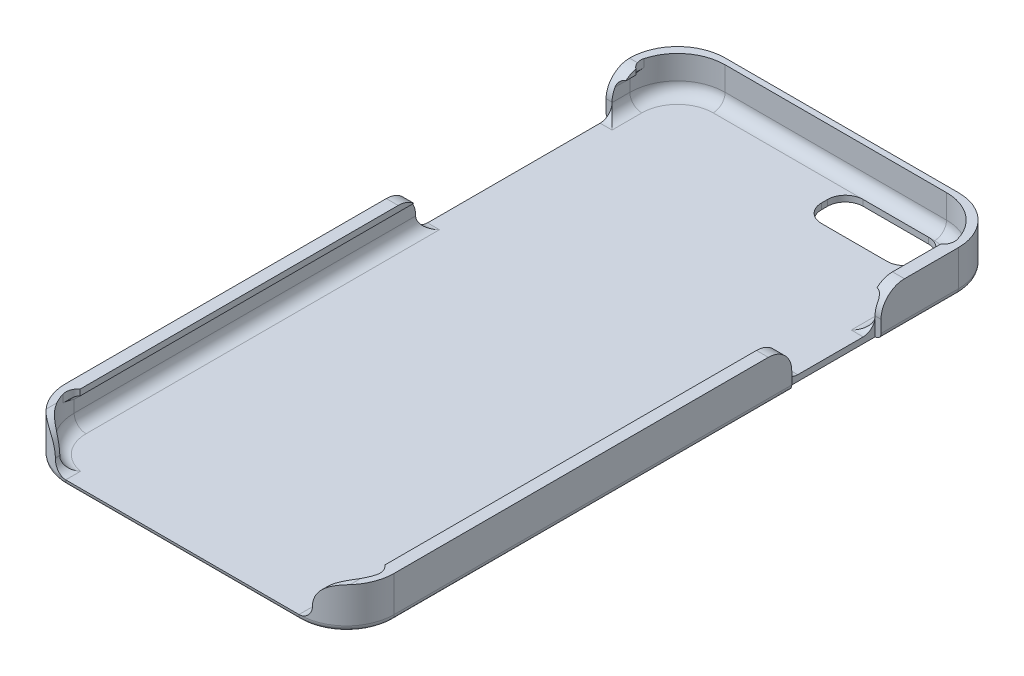
SolidWorks part; units mm, degrees
ref_plane "Front Plane" through (0, 0, 0) normal (0, 0, 1) x (1, 0, 0)
ref_plane "Top Plane" through (0, 0, 0) normal (0, 1, 0) x (1, 0, 0)
ref_plane "Right Plane" through (0, 0, 0) normal (1, 0, 0) x (0, 0, -1)
sketch "Sketch1" plane through (0, 0, 0) normal (0, 1, 0) x (1, 0, 0)
  line L1 (-35.052, 70.358) -> (35.052, 70.358)
  line L2 (-35.052, 70.358) -> (-35.052, -70.358)
  line L3 (-35.052, -70.358) -> (35.052, -70.358)
  line L4 (35.052, 70.358) -> (35.052, -70.358)
  line L5 (-35.052, 70.358) -> (35.052, -70.358) construction
  line L6 (-35.052, -70.358) -> (35.052, 70.358) construction
  point P0 (0, 0)
  dimension "D1" = 70.104
  dimension "D2" = 140.716
extrude "Boss-Extrude1" add sketch "Sketch1" along normal blind 1.27
sketch "Sketch2" plane through (0, 1.27, 0) normal (0, 1, 0) x (1, 0, 0)
  line L0 (-35.052, -70.358) -> (0, -70.358)
  line L1 (-35.052, -70.358) -> (35.052, -70.358) construction
  line L2 (-35.052, 70.358) -> (-35.052, -70.358)
  line L3 (-35.052, 70.358) -> (35.052, 70.358)
  line L4 (-33.782, 69.088) -> (-33.782, -69.088)
  line L5 (0, -70.358) -> (35.052, -70.358)
  line L6 (-33.782, -69.088) -> (33.782, -69.088)
  line L7 (35.052, 70.358) -> (35.052, -70.358)
  line L9 (33.782, 69.088) -> (33.782, -69.088)
  line L12 (-33.782, 69.088) -> (33.782, 69.088)
  dimension "D1" = 1.27
  dimension "D2" = 1.27
  dimension "D3" = 1.27
  dimension "D5" = 1.27
extrude "Boss-Extrude2" add sketch "Sketch2" along normal blind 7.62
sketch "Sketch3" plane through (-35.052, 0, 0) normal (-1, 0, 0) x (0, 0, 1)
  line L0 (-70.358, 8.89) -> (70.358, 8.89) construction
  line L1 (-55.118, 8.89) -> (-13.208, 8.89)
  line L2 (-55.118, 8.89) -> (-55.118, 1.27)
  line L3 (-55.118, 1.27) -> (-13.208, 1.27)
  line L4 (-13.208, 8.89) -> (-13.208, 1.27)
  line L5 (-70.358, 8.89) -> (-70.358, 0) construction
  line L6 (-70.358, 0) -> (70.358, 0) construction
  dimension "D1" = 15.24
  dimension "D2" = 57.15
  dimension "D3" = 1.27
extrude "Cut-Extrude1" cut sketch "Sketch3" against normal blind 1.27
sketch "Sketch5" plane through (35.052, 0, 0) normal (1, 0, 0) x (0, 0, -1)
  line L0 (-70.358, 8.89) -> (70.358, 8.89) construction
  line L1 (24.638, 8.89) -> (43.688, 8.89)
  line L2 (24.638, 8.89) -> (24.638, 1.27)
  line L3 (24.638, 1.27) -> (43.688, 1.27)
  line L4 (43.688, 8.89) -> (43.688, 1.27)
  line L5 (70.358, 8.89) -> (70.358, 0) construction
  line L6 (-70.358, 0) -> (70.358, 0) construction
  dimension "D1" = 26.67
  dimension "D2" = 45.72
  dimension "D3" = 1.27
extrude "Cut-Extrude2" cut sketch "Sketch5" against normal blind 1.27
sketch "Sketch6" plane through (0, 0, 70.358) normal (0, 0, 1) x (1, 0, 0)
  line L1 (-35.052, 8.89) -> (35.052, 8.89) construction
  line L2 (-27.432, 8.89) -> (27.432, 8.89)
  line L3 (-27.432, 8.89) -> (-27.432, 1.27)
  line L4 (-27.432, 1.27) -> (27.432, 1.27)
  line L8 (27.432, 8.89) -> (27.432, 1.27)
  line L9 (-35.052, 8.89) -> (-35.052, 0) construction
  line L10 (35.052, 8.89) -> (35.052, 0) construction
  line L11 (-35.052, 0) -> (35.052, 0) construction
  dimension "D1" = 7.62
  dimension "D2" = 7.62
  dimension "D3" = 1.27
extrude "Cut-Extrude3" cut sketch "Sketch6" against normal blind 1.27
sketch "Sketch7" plane through (0, 0, 0) normal (0, -1, 0) x (1, 0, 0)
  line L0 (35.052, 70.358) -> (35.052, -70.358) construction
  line L1 (26.162, -57.658) -> (4.572, -57.658)
  line L2 (26.162, -57.658) -> (26.162, -66.548)
  line L3 (26.162, -66.548) -> (4.572, -66.548)
  line L4 (4.572, -57.658) -> (4.572, -66.548)
  line L5 (35.052, -70.358) -> (-35.052, -70.358) construction
  dimension "D1" = 8.89
  dimension "D2" = 30.48
  dimension "D3" = 3.81
  dimension "D4" = 12.7
extrude "Cut-Extrude4" cut sketch "Sketch7" against normal blind 1.27
fillet "Fillet1" radius 10.16 4 edges at (33.782, 5.08, -69.088) (-33.782, 5.08, -69.088) (-33.782, 5.08, 69.088) (33.782, 5.08, 69.088)
fillet "Fillet2" radius 10.16 4 edges at (-35.052, 4.445, -70.358) (35.052, 4.445, -70.358) (35.052, 4.445, 70.358) (-35.052, 4.445, 70.358)
sketch "Sketch8" plane through (-33.782, 0, 0) normal (1, 0, 0) x (0, 0, -1)
  line L0 (58.928, 1.27) -> (58.928, 8.89) construction
  line L1 (55.118, 8.89) -> (58.928, 8.89)
  line L2 (55.118, 8.89) -> (55.118, 7.62)
  line L3 (55.118, 7.62) -> (58.928, 7.62)
  line L4 (58.928, 8.89) -> (58.928, 7.62)
  dimension "D1" = 1.27
extrude "Boss-Extrude3" add sketch "Sketch8" along normal blind 1.27
sketch "Sketch13" plane through (0, 0, -69.088) normal (0, 0, 1) x (1, 0, 0)
  line L0 (23.622, 1.27) -> (23.622, 8.89) construction
  line L1 (-23.622, 8.89) -> (23.622, 8.89)
  line L2 (-23.622, 8.89) -> (-23.622, 7.62)
  line L3 (-23.622, 7.62) -> (23.622, 7.62)
  line L4 (23.622, 8.89) -> (23.622, 7.62)
  dimension "D1" = 1.27
extrude "Boss-Extrude6" [suppressed] add sketch "Sketch13" along normal blind 1.27
sketch "Sketch14" plane through (33.782, 0, 0) normal (-1, 0, 0) x (0, 0, 1)
  line L0 (-43.688, 1.27) -> (-43.688, 8.89) construction
  line L1 (-58.928, 8.89) -> (-43.688, 8.89)
  line L2 (-58.928, 8.89) -> (-58.928, 7.62)
  line L3 (-58.928, 7.62) -> (-43.688, 7.62)
  line L4 (-43.688, 8.89) -> (-43.688, 7.62)
  dimension "D1" = 1.27
extrude "Boss-Extrude7" add sketch "Sketch14" along normal blind 1.27
sketch "Sketch19" plane through (33.782, 0, 0) normal (-1, 0, 0) x (0, 0, 1)
  line L1 (59.6694, 1.27) -> (59.6694, 8.89) construction
  line L2 (-24.638, 8.89) -> (59.6694, 8.89)
  line L3 (-24.638, 8.89) -> (-24.638, 7.62)
  line L4 (-24.638, 7.62) -> (59.6694, 7.62)
  line L5 (59.6694, 8.89) -> (59.6694, 7.62)
  dimension "D1" = 1.27
extrude "Boss-Extrude8" add sketch "Sketch19" along normal blind 1.27
sketch "Sketch20" plane through (-33.782, 0, 0) normal (1, 0, 0) x (0, 0, -1)
  line L1 (-59.6694, 8.89) -> (-59.6694, 1.27) construction
  line L2 (13.208, 8.89) -> (-59.6694, 8.89)
  line L3 (13.208, 8.89) -> (13.208, 7.62)
  line L4 (13.208, 7.62) -> (-59.6694, 7.62)
  line L5 (-59.6694, 8.89) -> (-59.6694, 7.62)
  dimension "D1" = 1.27
extrude "Boss-Extrude9" add sketch "Sketch20" along normal blind 1.27
fillet "Fillet9" radius 3.81 4 edges at (26.162, 0.635, -57.658) (26.162, 0.635, -66.548) (4.572, 0.635, -66.548) (4.572, 0.635, -57.658)
fillet "Fillet12" radius 1.27 8 edges at (32.0762, 0, 67.3822) (0, 0, 70.358) (-32.0762, 0, 67.3822) (-35.052, 0, 0) (-32.0762, 0, -67.3822) (0, 0, -70.358) (32.0762, 0, -67.3822) (35.052, 0, 0)
fillet "Fillet16" radius 2.54 9 edges at (33.782, 1.27, -51.308) (30.8062, 1.27, -66.1122) (-33.782, 1.27, -57.023) (-30.8062, 1.27, -66.1122) (33.782, 1.27, 17.5157) (-33.782, 1.27, 23.2307) (0, 1.27, -69.088) (32.0462, 1.27, 65.349) (-32.0462, 1.27, 65.349)
sketch "Sketch28" plane through (0, 1.27, 0) normal (0, 1, 0) x (1, 0, 0)
  line L0 (31.242, 24.638) -> (35.052, 24.638) construction
  line L1 (35.052, 43.688) -> (33.782, 43.688)
  line L2 (35.052, 43.688) -> (35.052, 24.638)
  line L3 (35.052, 24.638) -> (33.782, 24.638)
  line L4 (33.782, 43.688) -> (33.782, 24.638)
  line L5 (-31.242, 13.208) -> (-35.052, 13.208) construction
  line L6 (-35.052, 55.118) -> (-33.782, 55.118)
  line L7 (-35.052, 55.118) -> (-35.052, 13.208)
  line L8 (-35.052, 13.208) -> (-33.782, 13.208)
  line L9 (-33.782, 55.118) -> (-33.782, 13.208)
  dimension "D1" = 1.27
  dimension "D2" = 1.27
extrude "Cut-Extrude10" cut sketch "Sketch28" against normal blind 1.27
fillet "Fillet18" radius 1.27 4 edges at (33.782, 7.62, -51.308) (-33.782, 7.62, -57.023) (33.782, 7.62, 17.5157) (-33.782, 7.62, 23.2307)
fillet "Fillet28" radius 2.54 4 edges at (33.782, 7.62, 59.6694) (-33.782, 7.62, 59.6694) (33.782, 7.62, -58.928) (-33.782, 7.62, -58.928)
fillet "Fillet29" radius 5 6 edges at (27.432, 8.89, 69.5617) (-27.432, 8.89, 69.5617) (33.782, 8.89, -24.638) (33.782, 8.89, -43.688) (-33.782, 8.89, -13.208) (-33.782, 8.89, -55.118)
fillet "Fillet30" radius 2.54 6 edges at (-27.432, 1.27, 68.152) (27.432, 1.27, 68.152) (32.512, 1.27, -24.638) (32.512, 1.27, -43.688) (-32.512, 1.27, -13.208) (-32.512, 1.27, -55.118)
